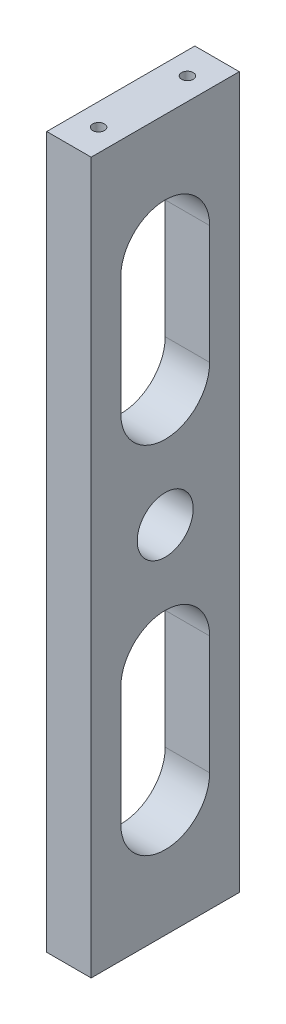
SolidWorks part; units mm, degrees
material "6061 Alloy"
ref_plane "Front Plane" through (0, 0, 0) normal (0, 0, 1) x (1, 0, 0)
ref_plane "Top Plane" through (0, 0, 0) normal (0, 1, 0) x (1, 0, 0)
ref_plane "Right Plane" through (0, 0, 0) normal (1, 0, 0) x (0, 0, -1)
sketch "Sketch1" plane through (0, 0, 0) normal (1, 0, 0) x (0, 0, -1)
  line L1 (-15.875, -76.2) -> (15.875, -76.2)
  line L2 (-15.875, -76.2) -> (-15.875, 76.2)
  line L3 (-15.875, 76.2) -> (15.875, 76.2)
  line L4 (15.875, -76.2) -> (15.875, 76.2)
  line L5 (-15.875, -76.2) -> (15.875, 76.2) construction
  line L6 (-15.875, 76.2) -> (15.875, -76.2) construction
  point P0 (0, 0)
  dimension "D1" = 31.75
  dimension "D2" = 152.4
extrude "Boss-Extrude1" add sketch "Sketch1" along normal mid plane 9.525
sketch "Sketch2" plane through (0, 76.2, 0) normal (0, 1, 0) x (1, 0, 0)
  line L0 (0, 9.525) -> (0, -9.525) construction
  line L1 (-4.7625, 15.875) -> (-4.7625, -15.875) construction
  line L2 (4.7625, 15.875) -> (-4.7625, 15.875) construction
  point P2 (0, 0)
  point P5 (-4.7625, 0)
  point P8 (0, 15.875)
  point P10 (0, 9.525)
  point P11 (0, -9.525)
  dimension "D1" = 19.05
hole_wizard "M3x0.5 Tapped Hole1" positions "Sketch3" profile "Sketch4" tap size "M3x0.5" standard "ANSI Metric"
sketch "Sketch3" plane through (0, 76.2, 0) normal (0, 1, 0) x (1, 0, 0)
  point P0 (0, 9.525)
  point P3 (0, -9.525)
sketch "Sketch4" plane through (0, 76.2, -9.525) normal (1, 0, 0) x (0, 0, 1)
  line L0 (0, 0) -> (0, 13.4511)
  line L1 (0, 13.4511) -> (1.25, 12.7)
  line L2 (1.25, 12.7) -> (1.25, 0)
  line L5 (1.25, 0) -> (0, 0)
  line L10 (0, 13.4511) -> (-1.25, 12.7) construction
  line L11 (0, -6.35) -> (0, 107.95) construction
  dimension "Tap Drill Dia." = 2.5
  dimension "Tap Drill Depth" = 12.7
  dimension "Drill Angle" = 118
cosmetic thread "Hole Thread1" parameters "D1"=6.096, "D2"=3
cosmetic thread "Hole Thread2" parameters "D1"=6.096, "D2"=3
mirror "Mirror1" about plane through (0, 0, 0) normal (0, 1, 0) of "M3x0.5 Tapped Hole1"
cosmetic thread "Hole Thread3" parameters "D1"=6.096, "D2"=3
cosmetic thread "Hole Thread4" parameters "D1"=6.096, "D2"=3
sketch "Sketch5" plane through (4.7625, 0, 0) normal (1, 0, 0) x (0, 0, -1)
  point P0 (0, 0)
hole_wizard "Ø12.0mm Dowel Hole1" positions "Sketch6" profile "Sketch8" hole size "Ø12.0" standard "ANSI Metric" end condition through all
sketch "Sketch6" plane through (4.7625, 0, 0) normal (1, 0, 0) x (0, 0, -1)
  point P0 (0, 0)
sketch "Sketch8" plane through (4.7625, 0, 0) normal (0, 1, 0) x (0, 0, -1)
  line L0 (0, 0) -> (0, 9.525)
  line L1 (0, 9.525) -> (6, 9.525)
  line L2 (6, 9.525) -> (6, 0)
  line L5 (6, 0) -> (0, 0)
  line L11 (0, -6.35) -> (0, 107.95) construction
  dimension "Thru Hole Dia." = 12
  dimension "Thru Hole Depth" = 9.525
sketch "Sketch9" plane through (4.7625, 0, 0) normal (1, 0, 0) x (0, 0, -1)
  line L0 (0, 50.8) -> (0, 25.4) construction
  line L1 (0, 55) -> (0, -55) construction
  line L2 (9.525, 50.8) -> (9.525, 25.4)
  line L3 (-9.525, 50.8) -> (-9.525, 25.4)
  line L4 (0, -25.4) -> (0, -50.8) construction
  line L5 (9.525, -25.4) -> (9.525, -50.8)
  line L6 (-9.525, -25.4) -> (-9.525, -50.8)
  line L7 (0, 25.4) -> (0, -25.4)
  line L8 (55, 0) -> (-55, 0) construction
  arc A0 (9.525, 50.8) -> (-9.525, 50.8) centre (0, 50.8) ccw
  arc A1 (-9.525, 25.4) -> (9.525, 25.4) centre (0, 25.4) ccw
  arc A2 (9.525, -25.4) -> (-9.525, -25.4) centre (0, -25.4) ccw
  arc A3 (-9.525, -50.8) -> (9.525, -50.8) centre (0, -50.8) ccw
  point P5 (0, 38.1)
  point P10 (0, -38.1)
  point P19 (0, 0)
  dimension "D1" = 25.4
  dimension "D2" = 19.05
  dimension "D3" = 25.4
extrude "Cut-Extrude1" cut sketch "Sketch9" against normal through all contours L6 A3 L5 A2 | L3 A1 L2 A0 region at (4.7625, -38.1, 0) region at (4.7625, 38.1, 0)
